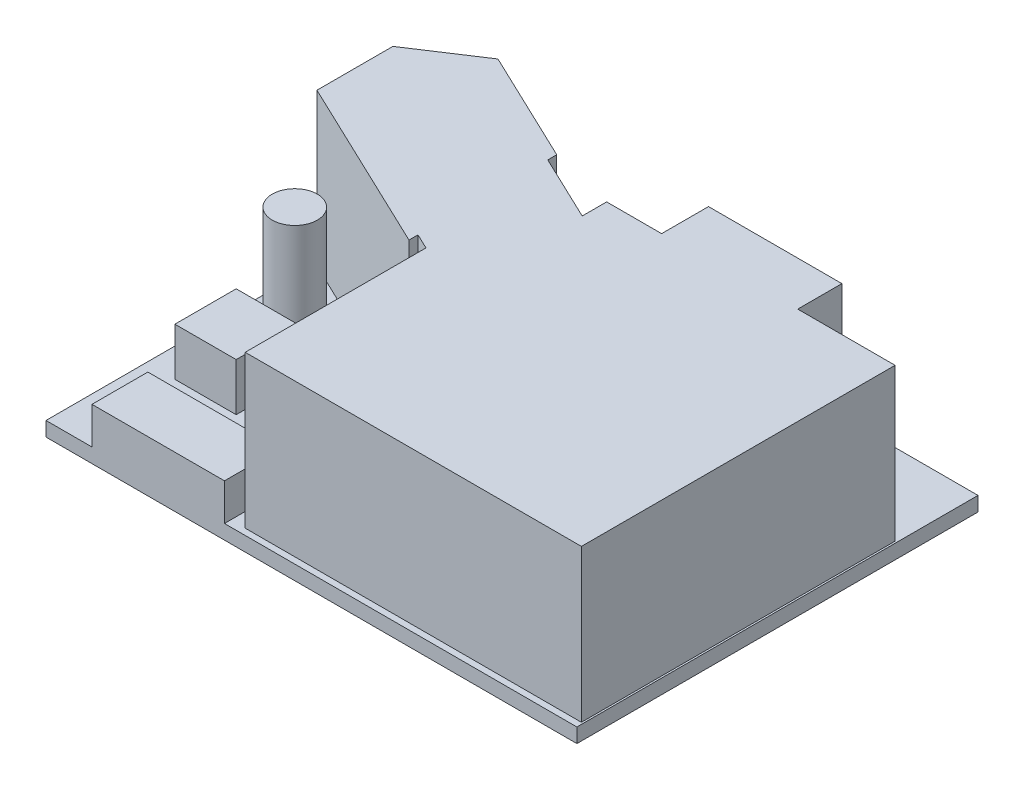
SolidWorks part; units mm, degrees
ref_plane "Front Plane" through (0, 0, 0) normal (0, 0, 1) x (1, 0, 0)
ref_plane "Top Plane" through (0, 0, 0) normal (0, 1, 0) x (1, 0, 0)
ref_plane "Right Plane" through (0, 0, 0) normal (1, 0, 0) x (0, 0, -1)
sketch "Sketch1" plane through (0, 0, 0) normal (0, 1, 0) x (1, 0, 0)
  line L1 (-17.0738, 18.4303) -> (41.8262, 18.4303)
  line L2 (-17.0738, 18.4303) -> (-17.0738, -26.0697)
  line L3 (-17.0738, -26.0697) -> (41.8262, -26.0697)
  line L4 (41.8262, 18.4303) -> (41.8262, -26.0697)
  dimension "D1" = 44.5
  dimension "D2" = 58.9
extrude "Boss-Extrude1" add sketch "Sketch1" along normal blind 1.6
sketch "Sketch2" plane through (0, 1.6, 0) normal (0, 1, 0) x (1, 0, 0)
  line L0 (-16.8738, 12.2122) -> (-16.8738, 3.7912)
  line L2 (4.3262, -5.3121) -> (4.3262, -25.3697)
  line L3 (4.3262, -25.3697) -> (41.6262, -25.3697)
  line L4 (41.6262, -25.3697) -> (41.6262, 9.4303)
  line L5 (41.6262, 9.4303) -> (30.8262, 9.4303)
  line L6 (30.8262, 9.4303) -> (30.8262, 14.3303)
  line L7 (30.8262, 14.3303) -> (16.0262, 14.3303)
  line L8 (16.0262, 14.3303) -> (16.0262, 9.1303)
  line L10 (-9.8322, 16.8303) -> (-16.8738, 12.2122)
  line L11 (16.0262, 9.1303) -> (9.9262, 9.1303)
  line L16 (-16.8738, 3.7912) -> (-9.8322, 16.8303) construction
  line L20 (9.9262, 9.1303) -> (9.9262, 6.4199)
  line L21 (-16.8738, 3.7912) -> (2.6262, -5.4991)
  line L24 (2.6262, -5.4991) -> (2.6262, -4.5021)
  line L25 (2.6262, -4.5021) -> (4.3262, -5.3121)
  line L26 (-9.8322, 16.8303) -> (2.6262, 10.8948)
  line L27 (2.6262, 10.8948) -> (2.6262, 9.8979)
  line L28 (2.6262, 9.8979) -> (9.9262, 6.4199)
  line L32 (2.6262, 10.8948) -> (2.6262, -5.4991) construction
  line L33 (-13.353, 10.3108) -> (-23.6207, 15.8558) construction
  line L35 (-17.0738, 18.4303) -> (-17.0738, -26.0697) construction
  line L36 (41.8262, 18.4303) -> (-17.0738, 18.4303) construction
  line L38 (-17.0738, -26.0697) -> (41.8262, -26.0697) construction
  point P13 (-18.8451, 11.9142)
  point P14 (-16.6146, 12.0489)
  point P15 (40.9563, -25.4866)
  point P27 (0, 0)
  dimension "D2" = 14.8
  dimension "D3" = 21.6
  dimension "D4" = 34.8
  dimension "D5" = 37.3
  dimension "D6" = 13.8
  dimension "D7" = 31.7
  dimension "D8" = 14.8
  dimension "D9" = 39.7
  dimension "D10" = 34.5
  dimension "D11" = 25.6
  dimension "D12" = 0.2
  dimension "D13" = 1.6
  dimension "D14" = 19.5
  dimension "D15" = 180
  dimension "D16" = 180
  dimension "D17" = 58.5
  dimension "D18" = 40.4
  dimension "D19" = 0.9
  dimension "D20" = 0.9
extrude "Boss-Extrude2" add sketch "Sketch2" along normal blind 16.9
sketch "Sketch3" plane through (0, 1.6, 0) normal (0, 1, 0) x (1, 0, 0)
  line L0 (-17.0738, -26.0697) -> (41.8262, -26.0697) construction
  line L1 (-13.8738, -8.1697) -> (-7.0738, -8.1697)
  line L2 (-13.8738, -8.1697) -> (-13.8738, -14.9697)
  line L3 (-13.8738, -14.9697) -> (-7.0738, -14.9697)
  line L4 (-7.0738, -8.1697) -> (-7.0738, -14.9697)
  line L5 (-3.6738, -8.1697) -> (3.1262, -8.1697)
  line L6 (-3.6738, -8.1697) -> (-3.6738, -14.9697)
  line L7 (-3.6738, -14.9697) -> (3.1262, -14.9697)
  line L8 (3.1262, -8.1697) -> (3.1262, -14.9697)
  line L9 (-11.9738, -26.0697) -> (2.7262, -26.0697)
  line L10 (-11.9738, -26.0697) -> (-11.9738, -19.8697)
  line L11 (-11.9738, -19.8697) -> (2.7262, -19.8697)
  line L12 (2.7262, -26.0697) -> (2.7262, -19.8697)
  line L13 (-17.0738, 18.4303) -> (-17.0738, -26.0697) construction
  circle A0 centre (-10.3738, -5.1697) radius 2.5
  line M31 (-17.0738, -26.0697) -> (41.8262, -26.0697)
  dimension "D12" = 5
  dimension "D1" = 14.7
  dimension "D2" = 19.8
  dimension "D3" = 6.8
  dimension "D4" = 6.8
  dimension "D5" = 6.8
  dimension "D6" = 6.8
  dimension "D7" = 6.2
  dimension "D8" = 4.9
  dimension "D9" = 4.9
  dimension "D10" = 3.2
  dimension "D11" = 3.4
  dimension "D13" = 6.7
  dimension "D14" = 20.9
extrude "Boss-Extrude3" add sketch "Sketch3" along normal blind 4.1 contours L12 L11 L10 M31 region at (-4.6238, 1.6, 22.9697)
extrude "Boss-Extrude4" add sketch "Sketch3<3>" along normal blind 5.3 contours L4 L1 L2 L3 | L8 L5 L6 L7 region at (-10.4738, 1.6, 11.5697) region at (-0.2738, 1.6, 11.5697)
sketch "Sketch3<3>" plane through (0, 1.6, 0) normal (0, 1, 0) x (1, 0, 0) same geometry as "Sketch3"
extrude "Boss-Extrude5" add sketch "Sketch3<4>" along normal blind 13.4 contours A0 region at (-10.3738, 1.6, 5.1697)
sketch "Sketch3<4>" plane through (0, 1.6, 0) normal (0, 1, 0) x (1, 0, 0) same geometry as "Sketch3"
